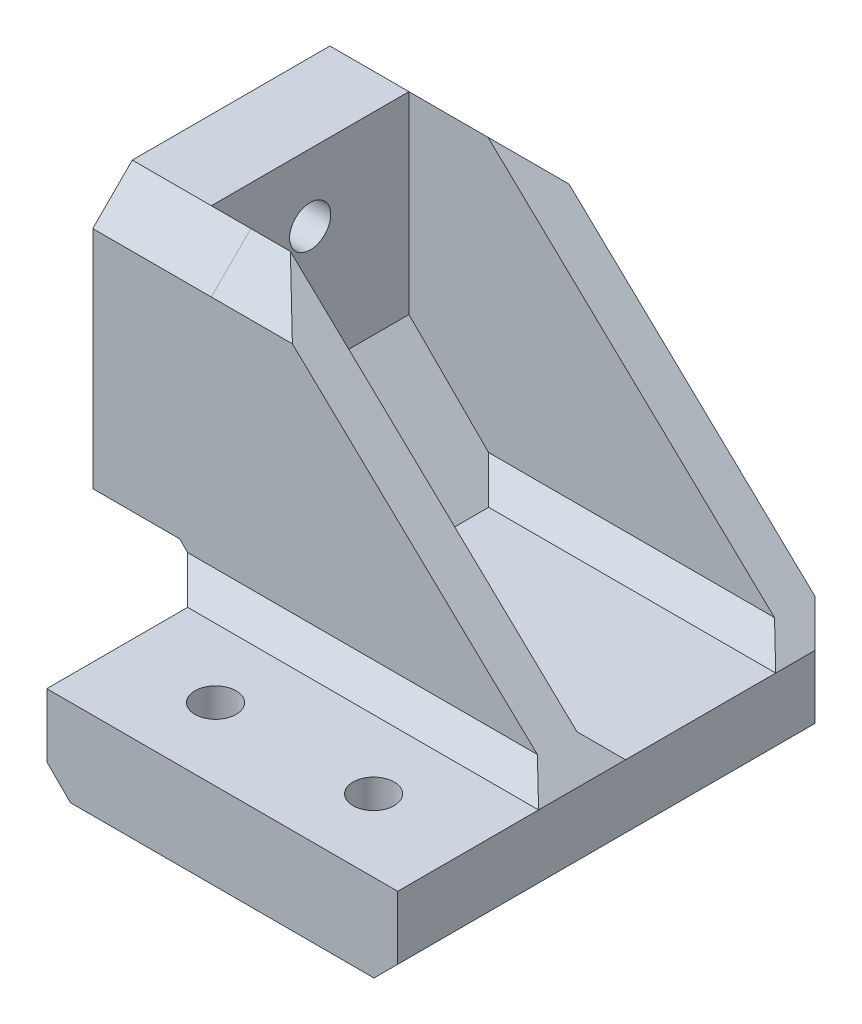
SolidWorks part; units mm, degrees
ref_plane "Front Plane" through (0, 0, 0) normal (0, 0, 1) x (1, 0, 0)
ref_plane "Top Plane" through (0, 0, 0) normal (0, 1, 0) x (1, 0, 0)
ref_plane "Right Plane" through (0, 0, 0) normal (1, 0, 0) x (0, 0, -1)
sketch "Sketch1" plane through (0, 0, 0) normal (0, 0, 1) x (1, 0, 0)
  line L0 (-22.2, 3) -> (-19.2, 0)
  line L1 (-19.2, 0) -> (19.2, 0)
  line L2 (19.2, 0) -> (22.2, 3)
  line L3 (22.2, 3) -> (22.2, 11)
  line L4 (22.2, 11) -> (-22.2, 11)
  line L5 (-22.2, 11) -> (-22.2, 3)
  line L6 (24.42, 0) -> (-24.42, 0) construction
sketch "Sketch2" plane through (0, 0, 0) normal (0, 1, 0) x (1, 0, 0)
  line L1 (-22.2, 0) -> (22.2, 0)
  line L2 (-22.2, 0) -> (-22.2, 55.82)
  line L3 (-22.2, 55.82) -> (22.2, 55.82)
  line L4 (22.2, 0) -> (22.2, 55.82)
  dimension "D1" = 55.82
extrude "Boss-Extrude1" add sketch "Sketch2" along normal up to vertex (11 mm away) up to point (22.2, 11, 0)
chamfer "Chamfer1" distance 3 angle 45 2 edges at (22.2, 0, -27.91) (-22.2, 0, -27.91)
sketch "Sketch3" plane through (0, 11, 0) normal (0, 1, 0) x (1, 0, 0)
  line L0 (0, 0) -> (0, 9.15) construction
  line L1 (0, 9.15) -> (10, 9.15) construction
  line L2 (0, 9.15) -> (-10, 9.15) construction
  circle A0 centre (10, 9.15) radius 2.6
  circle A1 centre (-10, 9.15) radius 2.6
  dimension "D4" = 5.2
  dimension "D5" = 5.2
  dimension "D1" = 9.15
  dimension "D2" = 10
  dimension "D3" = 10
extrude "Cut-Extrude1" cut sketch "Sketch3" against normal through all
sketch "Sketch4" plane through (-22.2, 0, 0) normal (-1, 0, 0) x (0, 0, 1)
  line L0 (-38.32, 48.5) -> (-38.32, 11) construction
  line L1 (-55.82, 11) -> (-20.82, 11)
  line L2 (-55.82, 11) -> (-55.82, 48.5)
  line L3 (-55.82, 48.5) -> (-20.82, 48.5)
  line L4 (-20.82, 11) -> (-20.82, 48.5)
  line L5 (-55.82, 40) -> (-20.82, 40) construction
  circle A0 centre (-38.32, 40) radius 2.6
  dimension "D3" = 5.2
  dimension "D1" = 37.5
  dimension "D2" = 35
  dimension "D4" = 29
extrude "Boss-Extrude2" add sketch "Sketch4" against normal blind 5 contours L2 L1 L4 L3 | A0
sketch "Sketch8" plane through (0, 0, -55.82) normal (0, 0, -1) x (-1, 0, 0)
  line L0 (-22.2, 11) -> (22.2, 11)
  line L1 (22.2, 11) -> (22.2, 48.5)
  line L2 (22.2, 48.5) -> (17.2, 48.5)
  line L3 (17.2, 48.5) -> (-22.2, 11)
extrude "Boss-Extrude7" add sketch "Sketch8" against normal blind 5
sketch "Sketch9" plane through (0, 0, -20.82) normal (0, 0, 1) x (1, 0, 0)
  line L0 (-22.2, 11) -> (-22.2, 48.5)
  line L1 (-22.2, 48.5) -> (-17.2, 48.5)
  line L2 (-17.2, 48.5) -> (22.2, 11)
  line L3 (22.2, 11) -> (-22.2, 11)
extrude "Boss-Extrude9" add sketch "Sketch9" against normal blind 5
chamfer "Chamfer8" distance 5 angle 45 2 edges at (-19.7, 48.5, -20.82) (-19.7, 48.5, -55.82)
sketch "Sketch11" plane through (-22.2, 0, 0) normal (-1, 0, 0) x (0, 0, 1)
  line L0 (-38.32, 40) -> (-38.32, 48.5) construction
  line L1 (-50.82, 48.5) -> (-25.82, 48.5) construction
sketch "Sketch12" plane through (-22.2, 0, 0) normal (-1, 0, 0) x (0, 0, 1)
  line L1 (-55.82, 48.5) -> (-20.82, 48.5)
  line L2 (-55.82, 48.5) -> (-55.82, 15)
  line L3 (-55.82, 15) -> (-20.82, 15)
  line L4 (-20.82, 48.5) -> (-20.82, 15)
  line L5 (-17.82, 11) -> (0, 11) construction
  line L6 (-50.82, 48.5) -> (-25.82, 48.5) construction
  line M8 (-20.82, 43.5) -> (-25.82, 48.5)
  line M9 (-25.82, 48.5) -> (-50.82, 48.5)
  line M10 (-50.82, 48.5) -> (-55.82, 43.5)
  circle M14 centre (-38.32, 40) radius 2.6
  dimension "D1" = 4
extrude "Boss-Extrude11" add sketch "Sketch12" along normal blind 15 contours L3 M8 M9 M10 M14 | L2 L3 L1 M10 | L4 L1 L3 M8 region at (-22.2, 46.8333, -54.1533) region at (-22.2, 31.2596, -38.32) region at (-22.2, 46.8333, -22.4867)
chamfer "Chamfer10" distance 5 angle 45 2 edges at (-29.7, 48.5, -20.82) (-29.7, 48.5, -55.82)
sketch "Sketch13" plane through (-17.2, 0, 0) normal (1, 0, 0) x (0, 0, -1)
  line L1 (25.82, 14) -> (50.82, 14)
  line L2 (25.82, 14) -> (25.82, 48.5)
  line L3 (25.82, 48.5) -> (50.82, 48.5)
  line L4 (50.82, 14) -> (50.82, 48.5)
extrude "Cut-Extrude2" cut sketch "Sketch13" against normal blind 10
sketch "Sketch14" plane through (0, 0, -20.82) normal (0, 0, 1) x (1, 0, 0)
  line L0 (-22.2, 15) -> (-26.2, 15)
  line L1 (-37.2, 15) -> (-22.2, 15) construction
  line L2 (-26.2, 15) -> (-22.2, 11)
  line L4 (-22.2, 11) -> (-22.2, 15)
  dimension "D1" = 4
  dimension "D2" = 4
extrude "Boss-Extrude12" add sketch "Sketch14" against normal up to surface (35 mm away) up to face at (-10.8547, 17.75, -55.82)
sketch "Sketch15" plane through (0, 0, -25.82) normal (0, 0, -1) x (-1, 0, 0)
  line L0 (14.1185, 11) -> (27.2, 24.0815)
  line L2 (27.2, 48.5) -> (27.2, 15) construction
  line L3 (27.2, 24.0815) -> (27.2, 15)
  line L4 (27.2, 15) -> (22.2, 15)
  line L5 (22.2, 15) -> (22.2, 11)
  line L6 (22.2, 11) -> (14.1185, 11)
  dimension "D1" = 18.5
  dimension "D2" = 45
extrude "Boss-Extrude13" add sketch "Sketch15" along normal up to surface (25 mm away) up to face at (-17.66, 24.05, -50.82)
chamfer "Chamfer11" distance 3 angle 45 6 edges at (4.0407, 11, -50.82) (4.0407, 11, -25.82) (0, 11, -20.82) (-22.2, 7, -55.82) (22.2, 7, -55.82) (0, 0, -55.82)
